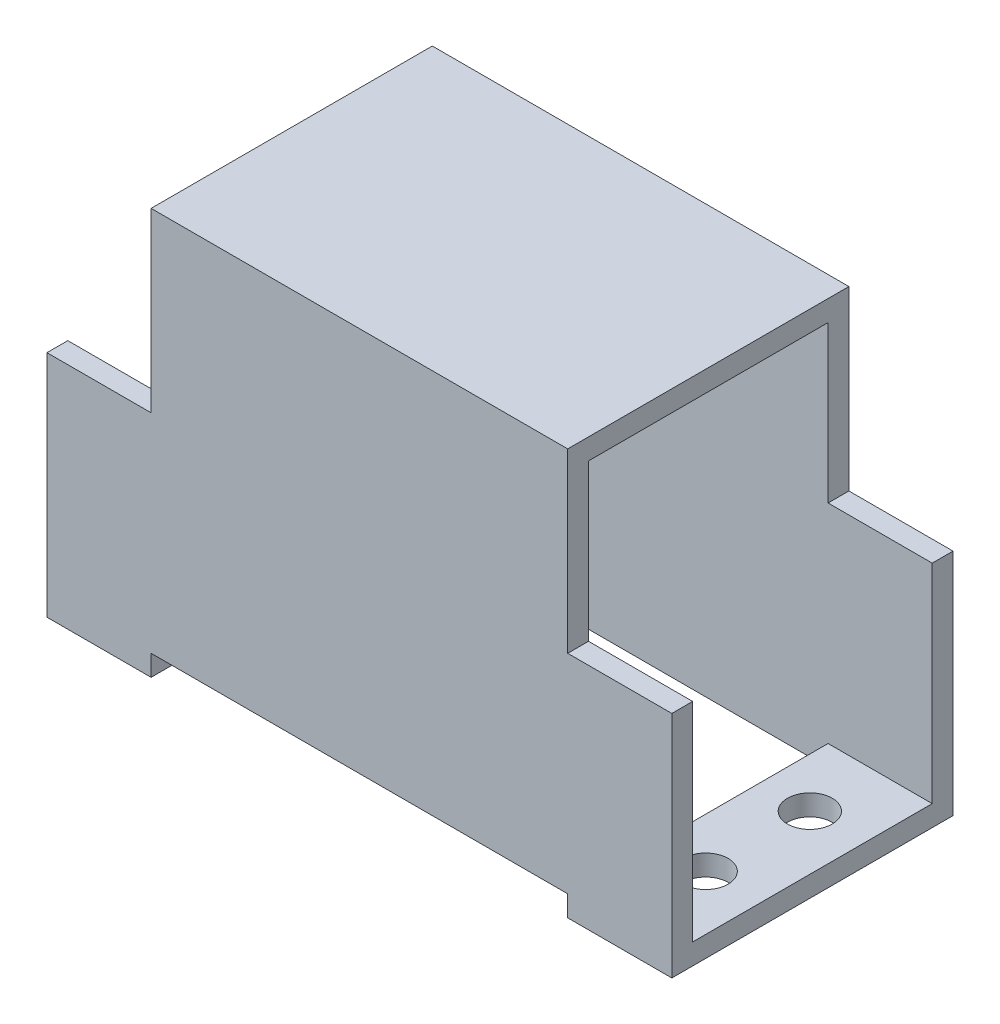
SolidWorks part; units mm, degrees
ref_plane "前视基准面" through (0, 0, 0) normal (0, 0, 1) x (1, 0, 0)
ref_plane "上视基准面" through (0, 0, 0) normal (0, 1, 0) x (1, 0, 0)
ref_plane "右视基准面" through (0, 0, 0) normal (1, 0, 0) x (0, 0, -1)
sketch "草图1" plane through (0, 0, 0) normal (0, 0, 1) x (1, 0, 0)
  line L0 (20, 2.5) -> (30, 2.5)
  line L1 (-20, -17.5) -> (20, -17.5)
  line L2 (-20, -17.5) -> (-20, 17.5)
  line L3 (-20, 17.5) -> (20, 17.5)
  line L4 (20, -17.5) -> (20, 17.5)
  line L5 (-20, -17.5) -> (20, 17.5) construction
  line L6 (-20, 17.5) -> (20, -17.5) construction
  line L7 (30, 2.5) -> (30, -17.5)
  line L8 (30, -17.5) -> (20, -17.5)
  line L9 (-20, -17.5) -> (-30, -17.5)
  line L10 (-30, -17.5) -> (-30, 2.5)
  line L11 (-30, 2.5) -> (-20, 2.5)
  line L12 (-30, -17.5) -> (-20, -17.5)
  point P0 (0, 0)
  dimension "D1" = 40
  dimension "D2" = 35
  dimension "D3" = 10
  dimension "D4" = 10
  dimension "D5" = 20
  dimension "D6" = 20
extrude "凸台-拉伸1" add sketch "草图1" along normal blind 2 contours L11 L10 L9 L2 | L1 L4 L3 L2 | L8 L7 L0 L4 region at (25, -7.5, 0) region at (0, 0, 0) region at (-25, -7.5, 0)
sketch "草图3" plane through (0, -17.5, 0) normal (0, -1, 0) x (1, 0, 0)
  line L0 (-30, 2) -> (-30, -23)
  line L2 (-20, -23) -> (-20, 2)
  line L3 (30, 2) -> (-30, 2) construction
  line L4 (-20, 2) -> (-30, 2)
  line L5 (30, -23) -> (30, 2)
  line L6 (30, 2) -> (20, 2)
  line L7 (20, 2) -> (20, -23)
  line L10 (-30, -23) -> (-20, -23)
  line L11 (20, -23) -> (30, -23)
  dimension "D1" = 10
  dimension "D2" = 25
  dimension "D3" = 10
extrude "凸台-拉伸2" add sketch "草图3" along normal blind 2
sketch "草图4" plane through (0, 0, -23) normal (0, 0, -1) x (-1, 0, 0)
  line L0 (30, -19.5) -> (30, -17.5) construction
  line L1 (-30, -19.5) -> (-30, -17.5) construction
  line L2 (30, -19.5) -> (30, -17.5)
  line L3 (-30, -19.5) -> (-30, -17.5)
  line L4 (-30, -19.5) -> (30, -19.5)
  line L10 (30, 2.5) -> (20, 2.5)
  line L11 (20, 2.5) -> (20, 17.5)
  line L12 (20, 17.5) -> (-20, 17.5)
  line L13 (-20, 17.5) -> (-20, 2.5)
  line L14 (-20, 2.5) -> (-30, 2.5)
  line L15 (-30, 2.5) -> (-30, -17.5)
  line L16 (-30, -17.5) -> (-20, -17.5)
  line L17 (-20, -17.5) -> (20, -17.5)
  line L18 (20, -17.5) -> (30, -17.5)
  line L19 (30, -17.5) -> (30, 2.5)
  line L20 (30, 2.5) -> (20, 2.5)
  line L21 (20, 2.5) -> (20, 17.5)
  line L22 (20, 17.5) -> (-20, 17.5)
  line L23 (-20, 17.5) -> (-20, 2.5)
  line L24 (-20, 2.5) -> (-30, 2.5)
  line L25 (-30, 2.5) -> (-30, -17.5)
  line L29 (30, -17.5) -> (30, 2.5)
  dimension "D1" = 0
extrude "凸台-拉伸3" add sketch "草图4" along normal blind 2
sketch "草图5" plane through (0, -17.5, 0) normal (0, 1, 0) x (1, 0, 0)
  line L0 (20, 0) -> (20, 23) construction
  line L1 (20, -2) -> (20, 23) construction
  line L2 (-20, 23) -> (-20, -2) construction
  line L3 (30, 11.5) -> (-30, 11.5) construction
  line L4 (30, 23) -> (30, 0) construction
  line L5 (-30, 0) -> (-30, 23) construction
  circle A0 centre (24.75, 16.5) radius 2.15
  circle A1 centre (24.75, 6.5) radius 2.15
  circle A2 centre (-24.75, 16.5) radius 2.15
  circle A3 centre (-24.75, 6.5) radius 2.15
  dimension "D2" = 4.3
  dimension "D3" = 4.3
  dimension "D7" = 4.3
  dimension "D8" = 4.3
  dimension "D1" = 4.75
  dimension "D4" = 4.75
  dimension "D5" = 4.75
  dimension "D6" = 4.75
  dimension "D9" = 5
  dimension "D10" = 5
  dimension "D11" = 5
  dimension "D12" = 5
extrude "切除-拉伸1" cut sketch "草图5" against normal up to next
sketch "草图6" plane through (0, 17.5, 0) normal (0, 1, 0) x (1, 0, 0)
  line L1 (-20, 0) -> (-20, -2) construction
  line L2 (-20, -2) -> (20, -2) construction
  line L3 (20, -2) -> (20, 0) construction
  line L5 (20, 23) -> (20, 25) construction
  line L6 (20, 25) -> (-20, 25) construction
  line L7 (-20, 25) -> (-20, 23) construction
  line L9 (-20, 0) -> (-20, -2)
  line L10 (-20, -2) -> (20, -2)
  line L11 (20, -2) -> (20, 0)
  line L13 (20, 23) -> (20, 25)
  line L14 (20, 25) -> (-20, 25)
  line L15 (-20, 25) -> (-20, 23)
  line L16 (-20, 23) -> (-20, 0)
  line L17 (20, 23) -> (20, 0)
extrude "凸台-拉伸5" add sketch "草图6" along normal blind 2
